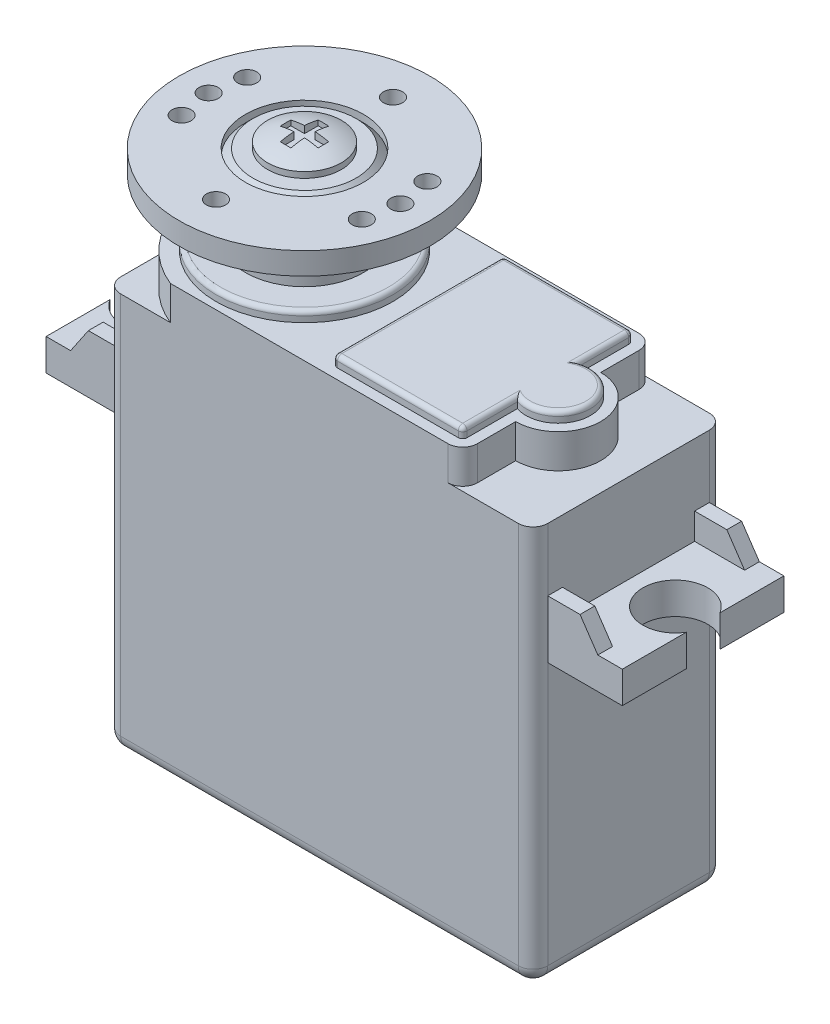
SolidWorks part; units mm, degrees
ref_plane "Front Plane" through (0, 0, 0) normal (0, 0, 1) x (1, 0, 0)
ref_plane "Top Plane" through (0, 0, 0) normal (0, 1, 0) x (1, 0, 0)
ref_plane "Right Plane" through (0, 0, 0) normal (1, 0, 0) x (0, 0, -1)
sketch "Sketch1" plane through (0, 0, 0) normal (0, 0, 1) x (1, 0, 0)
  line L0 (0, 14.1881) -> (0, -12.7839) construction
  line L1 (-14.478, -12.7839) -> (14.478, -12.7839)
  line L2 (-14.478, -12.7839) -> (-14.478, 14.1881)
  line L4 (14.478, -12.7839) -> (14.478, 14.1881)
  line L5 (-14.478, 14.1881) -> (14.478, 14.1881)
extrude "Boss-Extrude1" add sketch "Sketch1" along normal blind 6.477 and the other way blind 6.477
sketch "Sketch3" plane through (0, 14.1881, 0) normal (0, 1, 0) x (1, 0, 0)
  line L0 (14.478, 6.477) -> (-14.478, 6.477) construction
  line L1 (-10.1098, 6.477) -> (8.7105, 6.477)
  line L3 (-10.1098, -6.477) -> (8.7105, -6.477)
  line L4 (-1.4003, 0) -> (12.2029, 0) construction
  line L5 (14.478, -6.477) -> (-14.478, -6.477) construction
  line L6 (9.7105, 5.477) -> (9.7105, 2.8825)
  line L7 (9.7105, -5.477) -> (9.7105, -2.8825)
  line L8 (-14.478, 6.477) -> (-14.478, -6.477) construction
  arc A0 (9.7105, 2.8825) -> (9.7105, -2.8825) centre (9.7105, 0) cw
  arc A1 (9.7105, 5.477) -> (8.7105, 6.477) centre (8.7105, 5.477) ccw
  arc A3 (-10.1098, 6.477) -> (-10.1098, -6.477) centre (-7.4919, 0) ccw
  arc A4 (8.7105, -6.477) -> (9.7105, -5.477) centre (8.7105, -5.477) ccw
  point P16 (9.7105, 6.477)
  point P19 (-0.4757, 6.477)
  point P24 (9.7105, -6.477)
  dimension "D1" = 1
  dimension "D4" = 1
fillet "Fillet1" radius 1 4 edges at (14.478, 0.7021, -6.477) (14.478, 0.7021, 6.477) (-14.478, 0.7021, -6.477) (-14.478, 0.7021, 6.477)
fillet "Fillet2" radius 1 8 edges at (-14.1851, -12.7839, 6.1841) (-14.1851, -12.7839, -6.1841) (14.1851, -12.7839, -6.1841) (14.1851, -12.7839, 6.1841) (14.478, -12.7839, 0) (0, -12.7839, -6.477) (-14.478, -12.7839, 0) (0, -12.7839, 6.477)
extrude "Boss-Extrude2" add sketch "Sketch3" along normal blind 2.3
sketch "Sketch4" plane through (0, 16.4881, 0) normal (0, 1, 0) x (1, 0, 0)
  line L0 (9.0105, 2.0672) -> (9.0105, 5.477)
  line L1 (8.7105, 5.777) -> (0.5243, 5.777)
  line L2 (0.2243, 5.477) -> (0.2243, -5.477)
  line L3 (0.5243, -5.777) -> (8.7105, -5.777)
  line L4 (9.0105, -5.477) -> (9.0105, -2.0672)
  arc A0 (9.0105, 5.477) -> (8.7105, 5.777) centre (8.7105, 5.477) ccw
  arc A1 (0.5243, 5.777) -> (0.2243, 5.477) centre (0.5243, 5.477) ccw
  arc A2 (0.2243, -5.477) -> (0.5243, -5.777) centre (0.5243, -5.477) ccw
  arc A3 (8.7105, -5.777) -> (9.0105, -5.477) centre (8.7105, -5.477) ccw
  arc A4 (9.0105, -2.0672) -> (9.0105, 2.0672) centre (9.7105, 0) ccw
extrude "Boss-Extrude3" add sketch "Sketch4" along normal blind 0.7
fillet "Fillet3" radius 0.3 10 edges at (8.9227, 17.1881, -5.6891) (9.0105, 17.1881, -3.7721) (11.8931, 17.1881, 0) (9.0105, 17.1881, 3.7721) (8.9227, 17.1881, 5.6891) (4.6174, 17.1881, 5.777) (0.3121, 17.1881, 5.6891) (0.2243, 17.1881, 0) (0.3121, 17.1881, -5.6891) (4.6174, 17.1881, -5.777)
sketch "Sketch5" plane through (0, 16.4881, 0) normal (0, 1, 0) x (1, 0, 0)
  circle A0 centre (-7.4919, 0) radius 6
  dimension "D1" = 12
extrude "Boss-Extrude4" add sketch "Sketch5" along normal blind 0.7
fillet "Fillet4" radius 0.3 1 edges at (-13.4919, 17.1881, 0)
sketch "Sketch6" plane through (0, 17.1881, 0) normal (0, 1, 0) x (1, 0, 0)
  circle A0 centre (-7.4919, 0) radius 4
extrude "Boss-Extrude5" add sketch "Sketch6" along normal blind 5.3
chamfer "Chamfer1" distance 0.5 angle 45 1 edges at (-11.4919, 22.4881, 0)
sketch "Sketch7" plane through (0, 22.4881, 0) normal (0, 1, 0) x (1, 0, 0)
  circle A0 centre (-7.4919, 0) radius 4
  circle A1 centre (-7.4919, 0) radius 8.5
  dimension "D1" = 17
  dimension "D2" = 8
extrude "Boss-Extrude6" add sketch "Sketch7" against normal blind 1.5
sketch "Sketch8" plane through (0, 22.4881, 0) normal (0, 1, 0) x (1, 0, 0)
  circle A1 centre (-7.4919, 0) radius 8.5 construction
  circle A2 centre (-7.4919, -6) radius 0.65
  circle A3 centre (-7.4919, 6) radius 0.65
  dimension "D2" = 1.3
  dimension "D4" = 6
  dimension "D3" = 6
extrude "Cut-Extrude1" cut sketch "Sketch8" against normal up to surface (1.5 mm away) up to face at (-11.4919, 20.9881, 0)
sketch "Sketch9" plane through (0, 22.4881, 0) normal (0, 1, 0) x (1, 0, 0)
  line L0 (1.0081, 0) -> (-15.9919, 0) construction
  line L1 (-7.4919, -8.5) -> (-7.4919, 8.5) construction
  circle A0 centre (-13.9919, 0) radius 0.65
  circle A1 centre (-7.4919, 0) radius 8.5 construction
  circle A2 centre (-0.9919, 0) radius 0.65
  dimension "D1" = 1.3
  dimension "D2" = 6.5
extrude "Cut-Extrude2" cut sketch "Sketch9" against normal up to surface (1.5 mm away) up to face at (-8.1419, 20.9881, -6)
pattern_circular "CirPattern1" count 2 over 20 about axis through (-7.4919, 22.4881, 0) along (0, 1, 0) of "Cut-Extrude2"
pattern_circular "CirPattern2" count 2 over 20 about axis through (-7.4919, 22.4881, 0) along (0, 1, 0) of "Cut-Extrude2" reverse direction yes
sketch "Sketch11" plane through (0, 0, 0) normal (0, 0, 1) x (1, 0, 0)
  line L0 (-4.9919, 22.4881) -> (-4.9919, 22.8881)
  line L2 (-7.4919, 22.4881) -> (-7.4919, 25.726) construction
  line L3 (-7.4919, 23.4881) -> (-7.4919, 22.4881)
  line L4 (-3.9919, 22.4881) -> (-10.9919, 22.4881) construction
  line L5 (-7.4919, 22.4881) -> (-4.9919, 22.4881)
  spline S0 degree 2 poles (-4.9919, 22.8881) (-6.1583, 23.4881) (-7.4919, 23.4881) knots 0 0 0 1 1 1
  dimension "D1" = 2.5
  dimension "D2" = 0.4
  dimension "D3" = 0.6
revolve "Revolve1" add sketch "Sketch11" angle 360 about L2
ref_plane "Plane1" through (0, 23.4881, 0) normal (0, 1, 0) x (1, 0, 0)
sketch "Sketch12" plane through (0, 23.4881, 0) normal (0, 1, 0) x (1, 0, 0)
  line L0 (-7.1311, -1.2853) -> (-7.1311, -0.3609)
  line L2 (-6.2066, 0.3609) -> (-6.2066, -0.3609)
  line L4 (-8.7773, 0.3609) -> (-8.7773, -0.3609)
  line L7 (-7.1311, 1.2853) -> (-7.8528, 1.2853)
  line L9 (-7.1311, -1.2853) -> (-7.8528, -1.2853)
  line L13 (-7.1311, -0.3609) -> (-6.2066, -0.3609)
  line L14 (-6.2066, 0.3609) -> (-7.1311, 0.3609)
  line L15 (-7.1311, 0.3609) -> (-7.1311, 1.2853)
  line L16 (-7.8528, 1.2853) -> (-7.8528, 0.3609)
  line L17 (-7.8528, 0.3609) -> (-8.7773, 0.3609)
  line L19 (-8.7773, -0.3609) -> (-7.8528, -0.3609)
  line L20 (-7.8528, -0.3609) -> (-7.8528, -1.2853)
  point P0 (-7.4919, 0)
  point P6 (-7.4919, 0)
extrude "Cut-Extrude3" cut sketch "Sketch12" against normal blind 0.5
sketch "Sketch14" plane through (0, 0, 0) normal (0, 0, 1) x (1, 0, 0)
  line L0 (-14.478, 6.0121) -> (-19.5338, 6.0121)
  line L1 (-14.478, -11.7839) -> (-14.478, 14.1881) construction
  line L2 (-19.5338, 6.0121) -> (-19.5338, 8.1579)
  line L3 (-19.5338, 8.1579) -> (-17.8715, 8.1579)
  line L4 (-17.8715, 8.1579) -> (-16.6669, 9.9366)
  line L5 (-16.6669, 9.9366) -> (-14.478, 9.9366)
  line L6 (-14.478, 9.9366) -> (-14.478, 6.0121)
  line L7 (13.478, -12.7839) -> (-13.478, -12.7839) construction
  line L8 (0, -12.7839) -> (0, 26.1144) construction
  line L9 (19.5338, 6.0121) -> (19.5338, 8.1579)
  line L10 (19.5338, 8.1579) -> (17.8715, 8.1579)
  line L11 (17.8715, 8.1579) -> (16.6669, 9.9366)
  line L12 (16.6669, 9.9366) -> (14.478, 9.9366)
  line L13 (14.478, 9.9366) -> (14.478, 6.0121)
  line L14 (14.478, 6.0121) -> (19.5338, 6.0121)
  dimension "D1" = 18.796
extrude "Boss-Extrude7" add sketch "Sketch14" along normal offset from surface 1 and the other way offset from surface 1 up to face at (0.1586, 8.5576, 6.477) other way up to face at (0.1586, 8.5576, -6.477)
sketch "Sketch16" plane through (-19.5338, 0, 0) normal (-1, 0, 0) x (0, 0, 1)
  line L0 (5.477, 8.1579) -> (-5.477, 8.1579) construction
  line L1 (-4.477, 8.1579) -> (4.477, 8.1579)
  line L2 (-4.477, 8.1579) -> (-4.477, 12.1696)
  line L3 (-4.477, 12.1696) -> (4.477, 12.1696)
  line L4 (4.477, 8.1579) -> (4.477, 12.1696)
  line L5 (-5.477, 8.1579) -> (-5.477, 6.0121) construction
  line L6 (5.477, 6.0121) -> (5.477, 8.1579) construction
  dimension "D1" = 1
  dimension "D2" = 1
extrude "Cut-Extrude4" cut sketch "Sketch16" against normal up to surface (5.0558 mm away) up to face at (-14.478, 12.4875, 0)
sketch "Sketch17" plane through (19.5338, 0, 0) normal (1, 0, 0) x (0, 0, -1)
  line L0 (-5.477, 8.1579) -> (5.477, 8.1579) construction
  line L1 (-4.477, 8.1579) -> (4.477, 8.1579)
  line L2 (-4.477, 8.1579) -> (-4.477, 11.5385)
  line L3 (-4.477, 11.5385) -> (4.477, 11.5385)
  line L4 (4.477, 8.1579) -> (4.477, 11.5385)
  line L5 (-5.477, 8.1579) -> (-5.477, 6.0121) construction
  line L6 (5.477, 6.0121) -> (5.477, 8.1579) construction
  dimension "D1" = 1
  dimension "D2" = 1
extrude "Cut-Extrude5" cut sketch "Sketch17" against normal up to surface (5.0558 mm away) up to face at (14.478, 12.0624, 0)
sketch "Sketch18" plane through (0, 8.1579, 0) normal (0, 1, 0) x (1, 0, 0)
  line L0 (14.478, 5.477) -> (14.478, -5.477) construction
  line L1 (0, -17.8746) -> (0, 16.7815) construction
  circle A0 centre (17.653, 0) radius 2.2
  circle A1 centre (-17.653, 0) radius 2.2
  dimension "D2" = 4.4
  dimension "D1" = 3.175
extrude "Cut-Extrude6" cut sketch "Sketch18" against normal through all
